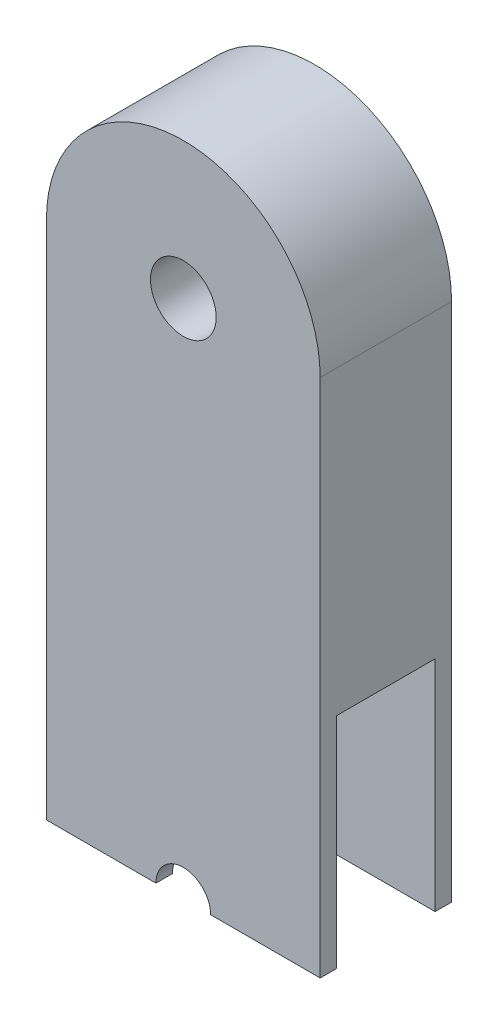
SolidWorks part; units mm, degrees
material "ABS"
ref_plane "Front Plane" through (0, 0, 0) normal (0, 0, 1) x (1, 0, 0)
ref_plane "Top Plane" through (0, 0, 0) normal (0, 1, 0) x (1, 0, 0)
ref_plane "Right Plane" through (0, 0, 0) normal (1, 0, 0) x (0, 0, -1)
sketch "Sketch1" plane through (0, 0, 0) normal (1, 0, 0) x (0, 0, -1)
  line L1 (0, 0) -> (-24, 0)
  line L2 (0, 0) -> (0, -120)
  line L3 (0, -120) -> (-24, -120)
  line L4 (-24, 0) -> (-24, -120)
  dimension "D1" = 120
  dimension "D2" = 24
extrude "Boss-Extrude1" add sketch "Sketch1" along normal blind 50
sketch "Sketch3" plane through (0, 0, 24) normal (0, 0, 1) x (1, 0, 0)
  line L0 (25, 0) -> (25, -120) construction
  line L1 (50, 0) -> (0, 0) construction
  line L2 (50, -120) -> (0, -120) construction
  circle A0 centre (25, -25) radius 6
  dimension "D1" = 12
  dimension "D2" = 25
extrude "Cut-Extrude1" cut sketch "Sketch3" against normal through all
sketch "Sketch4" plane through (50, 0, 0) normal (1, 0, 0) x (0, 0, -1)
  line L0 (-12, 0) -> (-12, -120) construction
  line L1 (0, 0) -> (-24, 0) construction
  line L2 (-24, -120) -> (0, -120) construction
  line L4 (-21, -80) -> (-3, -80)
  line L5 (-21, -80) -> (-21, -160)
  line L6 (-21, -160) -> (-3, -160)
  line L7 (-3, -80) -> (-3, -160)
  line L8 (-21, -80) -> (-3, -160) construction
  line L9 (-21, -160) -> (-3, -80) construction
  dimension "D1" = 80
  dimension "D2" = 18
sketch "Sketch5" plane through (0, 0, 24) normal (0, 0, 1) x (1, 0, 0)
  line L0 (25, -120) -> (25, 0) construction
  line L1 (50, -120) -> (0, -120) construction
  line L2 (50, 0) -> (0, 0) construction
  circle A0 centre (25, -120) radius 5
  dimension "D1" = 10
extrude "Cut-Extrude4" cut sketch "Sketch5" against normal through all
extrude "Cut-Extrude5" cut sketch "Sketch4" against normal through all
sketch "Sketch6" plane through (0, 0, 24) normal (0, 0, 1) x (1, 0, 0)
  line L0 (0, 0) -> (0, -120) construction
  line L1 (50, 0) -> (50, -120) construction
  arc A0 (0, -25) -> (50, -25) centre (25, -25) cw
extrude "Cut-Extrude7" cut sketch "Sketch6" against normal through all and the other way through all
fillet "Fillet2" radius 1 1 edges at (31, -25, 0)
